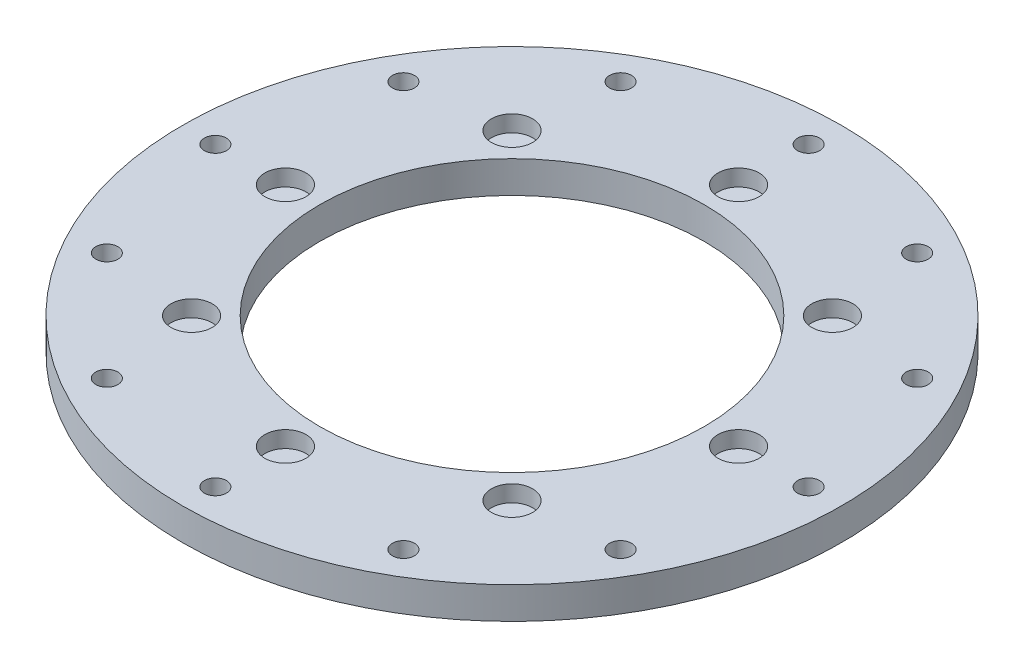
SolidWorks part; units mm, degrees
ref_plane "Front Plane" through (0, 0, 0) normal (0, 0, 1) x (1, 0, 0)
ref_plane "Top Plane" through (0, 0, 0) normal (0, 1, 0) x (1, 0, 0)
ref_plane "Right Plane" through (0, 0, 0) normal (1, 0, 0) x (0, 0, -1)
sketch "Sketch1" plane through (0, 0, 0) normal (0, 1, 0) x (1, 0, 0)
  circle A0 centre (0, 0) radius 60
  circle A1 centre (0, 0) radius 35
  dimension "D1" = 120
  dimension "D2" = 70
extrude "Boss-Extrude1" add sketch "Sketch1" along normal blind 5.8
sketch "Sketch3" plane through (0, 5.8, 0) normal (0, 1, 0) x (1, 0, 0)
  line L0 (0, 0) -> (27, 46.7654) construction
  line L1 (0, 0) -> (0, 54) construction
  circle A0 centre (0, 0) radius 54 construction
  circle A1 centre (0, 54) radius 2
  circle A2 centre (27, 46.7654) radius 2
  circle A3 centre (46.7654, 27) radius 2
  circle A4 centre (54, 0) radius 2
  circle A5 centre (46.7654, -27) radius 2
  circle A6 centre (27, -46.7654) radius 2
  circle A7 centre (0, -54) radius 2
  circle A8 centre (-27, -46.7654) radius 2
  circle A9 centre (-46.7654, -27) radius 2
  circle A10 centre (-54, 0) radius 2
  circle A11 centre (-46.7654, 27) radius 2
  circle A12 centre (-27, 46.7654) radius 2
  point P17 (0, 0)
  dimension "D1" = 108
  dimension "D2" = 4
  dimension "D4" = 30
  dimension "D3" = 12
extrude "Cut-Extrude2" cut sketch "Sketch3" against normal through all
sketch "Sketch4" plane through (0, 5.8, 0) normal (0, 1, 0) x (1, 0, 0)
  line L0 (0, 0) -> (41.25, 0) construction
  line L1 (29.1682, 29.1682) -> (0, 0) construction
  circle A0 centre (0, 0) radius 41.25 construction
  circle A1 centre (41.25, 0) radius 3.75
  circle A2 centre (29.1682, -29.1682) radius 3.75
  circle A3 centre (0, -41.25) radius 3.75
  circle A4 centre (-29.1682, -29.1682) radius 3.75
  circle A5 centre (-41.25, 0) radius 3.75
  circle A6 centre (-29.1682, 29.1682) radius 3.75
  circle A7 centre (0, 41.25) radius 3.75
  circle A8 centre (29.1682, 29.1682) radius 3.75
  point P5 (0, 0)
  point P22 (0, 0)
  dimension "D1" = 82.5
  dimension "D2" = 7.5
  dimension "D4" = 45
  dimension "D3" = 8
extrude "Cut-Extrude3" cut sketch "Sketch4" against normal blind 3
